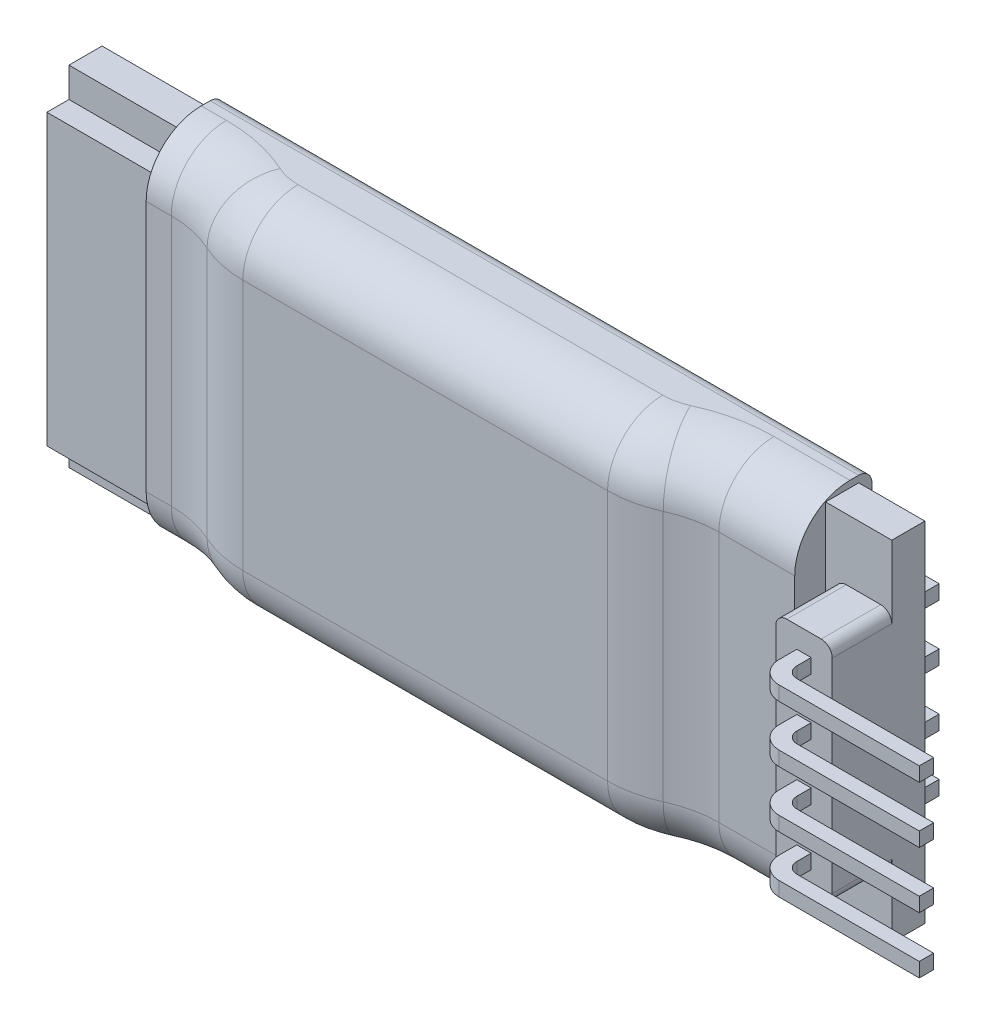
SolidWorks part; units mm, degrees
ref_plane "Přední rovina" through (0, 0, 0) normal (0, 0, 1) x (1, 0, 0)
ref_plane "Horní rovina" through (0, 0, 0) normal (0, 1, 0) x (1, 0, 0)
ref_plane "Pravá rovina" through (0, 0, 0) normal (1, 0, 0) x (0, 0, -1)
sketch "Skica1" plane through (0, 0, 0) normal (0, 0, 1) x (1, 0, 0)
  line L0 (0, 0) -> (-5.05, 0) construction
  line L1 (18.65, -7.9) -> (-18.65, -7.9)
  line L2 (18.65, -7.9) -> (18.65, 7.9)
  line L3 (18.65, 7.9) -> (-18.65, 7.9)
  line L4 (-18.65, -7.9) -> (-18.65, 7.9)
  line L5 (18.65, -7.9) -> (-18.65, 7.9) construction
  line L6 (18.65, 7.9) -> (-18.65, -7.9) construction
  line L7 (8.55, -6.55) -> (-18.65, -6.55)
  line L8 (8.55, -6.55) -> (8.55, 6.55)
  line L9 (8.55, 6.55) -> (-18.65, 6.55)
  line L10 (-18.65, -6.55) -> (-18.65, 6.55)
  line L11 (8.55, -6.55) -> (-18.65, 6.55) construction
  line L12 (8.55, 6.55) -> (-18.65, -6.55) construction
  point P0 (0, 0)
  point P6 (-5.05, 0)
  dimension "D1" = 15.8
  dimension "D2" = 37.3
  dimension "D3" = 13.1
  dimension "D4" = 27.2
extrude "Přidat vysunutím1" add sketch "Skica1" against normal blind 1.5 contours L3 L4 L1 L2
extrude "Přidat vysunutím2" add sketch "Skica1<3>" along normal blind 1 contours L8 L9 L4 L7 region at (-5.05, 0, 0)
sketch "Skica1<3>" plane through (0, 0, 0) normal (0, 0, 1) x (1, 0, 0) same geometry as "Skica1"
sketch "Skica2" plane through (0, 0, 0) normal (0, 0, 1) x (1, 0, 0)
  line L0 (18.65, -7.9) -> (18.65, 7.9) construction
  line L1 (16.09, -5.12) -> (18.65, -5.12)
  line L2 (16.09, -5.12) -> (16.09, 5.12)
  line L3 (16.09, 5.12) -> (18.65, 5.12)
  line L4 (18.65, -5.12) -> (18.65, 5.12)
  line L5 (16.09, -5.12) -> (18.65, 5.12) construction
  line L6 (16.09, 5.12) -> (18.65, -5.12) construction
  line L7 (0, 0) -> (17.37, 0) construction
  point P0 (17.37, 0)
  dimension "D1" = 2.56
  dimension "D2" = 10.24
extrude "Přidat vysunutím3" add sketch "Skica2" along normal blind 2.7
sketch "Skica3" plane through (0, 0, 2.7) normal (0, 0, 1) x (1, 0, 0)
  line L0 (18.65, 0) -> (16.09, 0) construction
  line L1 (18.65, -5.12) -> (18.65, 5.12) construction
  line L2 (16.09, 5.12) -> (16.09, -5.12) construction
  line L3 (17.37, -5.12) -> (17.37, 5.12) construction
  line L4 (16.09, -5.12) -> (18.65, -5.12) construction
  line L5 (18.65, 5.12) -> (16.09, 5.12) construction
  line L6 (17.695, 1.605) -> (17.045, 0.955) construction
  line L7 (17.695, -3.515) -> (17.045, -3.515)
  line L8 (17.695, -3.515) -> (17.695, -4.165)
  line L9 (17.695, -4.165) -> (17.045, -4.165)
  line L10 (17.045, -3.515) -> (17.045, -4.165)
  line L11 (17.695, -3.515) -> (17.045, -4.165) construction
  line L12 (17.695, -4.165) -> (17.045, -3.515) construction
  line L13 (17.695, -0.955) -> (17.045, -0.955)
  line L14 (17.695, -0.955) -> (17.695, -1.605)
  line L15 (17.695, -1.605) -> (17.045, -1.605)
  line L16 (17.045, -0.955) -> (17.045, -1.605)
  line L17 (17.695, -0.955) -> (17.045, -1.605) construction
  line L18 (17.695, -1.605) -> (17.045, -0.955) construction
  line L19 (17.695, 0.955) -> (17.045, 1.605) construction
  line L20 (17.695, 4.165) -> (17.045, 3.515) construction
  line L21 (17.695, 3.515) -> (17.045, 4.165) construction
  line L22 (17.045, 0.955) -> (17.045, 1.605)
  line L23 (17.695, 1.605) -> (17.045, 1.605)
  line L24 (17.695, 0.955) -> (17.695, 1.605)
  line L25 (17.695, 0.955) -> (17.045, 0.955)
  line L26 (17.045, 3.515) -> (17.045, 4.165)
  line L27 (17.695, 4.165) -> (17.045, 4.165)
  line L28 (17.695, 3.515) -> (17.695, 4.165)
  line L29 (17.695, 3.515) -> (17.045, 3.515)
  point P12 (17.37, -3.84)
  point P17 (17.37, -1.28)
  point P30 (17.37, 1.28)
  point P31 (17.37, 3.84)
  dimension "D1" = 0.65
  dimension "D2" = 2.56
  dimension "D3" = 2.56
extrude "Přidat vysunutím4" add sketch "Skica3" along normal blind 1.8 and the other way blind 5.8
sketch "Skica4" plane through (17.695, 0, 0) normal (1, 0, 0) x (0, 0, -1)
  line L0 (-2.7, -3.515) -> (-4.5, -3.515) construction
  line L1 (-4.5, -4.165) -> (-3.85, -4.165)
  line L2 (-4.5, -4.165) -> (-4.5, -3.515)
  line L3 (-4.5, -3.515) -> (-3.85, -3.515)
  line L4 (-3.85, -4.165) -> (-3.85, -3.515)
  line L5 (-2.7, -0.955) -> (-4.5, -0.955) construction
  line L6 (-4.5, -1.605) -> (-3.85, -1.605)
  line L7 (-4.5, -1.605) -> (-4.5, -0.955)
  line L8 (-4.5, -0.955) -> (-3.85, -0.955)
  line L9 (-3.85, -1.605) -> (-3.85, -0.955)
  line L10 (0, 0) -> (-5.4142, 0) construction
  line L11 (-3.85, 1.605) -> (-3.85, 0.955)
  line L12 (-4.5, 0.955) -> (-3.85, 0.955)
  line L13 (-4.5, 1.605) -> (-4.5, 0.955)
  line L14 (-4.5, 1.605) -> (-3.85, 1.605)
  line L15 (-3.85, 4.165) -> (-3.85, 3.515)
  line L16 (-4.5, 3.515) -> (-3.85, 3.515)
  line L17 (-4.5, 4.165) -> (-4.5, 3.515)
  line L18 (-4.5, 4.165) -> (-3.85, 4.165)
extrude "Přidat vysunutím5" add sketch "Skica4" along normal blind 6.7
fillet "Zaoblit1" radius 1 4 edges at (17.045, -3.84, 4.5) (17.045, -1.28, 4.5) (17.045, 1.28, 4.5) (17.045, 3.84, 4.5)
fillet "Zaoblit2" radius 0.5 4 edges at (17.695, 3.84, 3.85) (17.695, 1.28, 3.85) (17.695, -1.28, 3.85) (17.695, -3.84, 3.85)
sketch "Skica5" plane through (0, 0, -1.5) normal (0, 0, -1) x (-1, 0, 0)
  line L0 (18.65, -7.9) -> (18.65, 7.9) construction
  line L1 (-15.65, 8.2) -> (13.75, 8.2)
  line L2 (-15.65, 8.2) -> (-15.65, -8.2)
  line L3 (-15.65, -8.2) -> (13.75, -8.2)
  line L4 (13.75, 8.2) -> (13.75, -8.2)
  line L5 (-15.65, 8.2) -> (13.75, -8.2) construction
  line L6 (-15.65, -8.2) -> (13.75, 8.2) construction
  line L7 (-18.65, -7.9) -> (-18.65, 7.9) construction
  line L8 (-0.95, 0) -> (0, 0) construction
  point P0 (-0.95, 0)
  dimension "D1" = 4.9
  dimension "D2" = 3
  dimension "D3" = 16.4
extrude "Přidat vysunutím6" add sketch "Skica5" along normal blind 0.6 and the other way blind 3.8
sketch "Skica6" plane through (0, 0, 2.3) normal (0, 0, 1) x (1, 0, 0)
  line L0 (-13.75, 8.2) -> (15.65, 8.2) construction
  line L1 (15.65, -8.2) -> (9.35, -8.2)
  line L2 (15.65, -8.2) -> (15.65, 8.2)
  line L3 (15.65, 8.2) -> (9.35, 8.2)
  line L4 (9.35, -8.2) -> (9.35, 8.2)
  dimension "D1" = 6.3
extrude "Odebrat vysunutím1" cut sketch "Skica6" against normal blind 0.9
fillet "Zaoblit3" radius 5 1 edges at (9.35, 0, 1.4)
fillet "Zaoblit4" radius 5 1 edges at (9.35, 0, 2.3)
sketch "Skica7" plane through (0, 0, 2.3) normal (0, 0, 1) x (1, 0, 0)
  line L0 (8.0657, -8.2) -> (-13.75, -8.2) construction
  line L1 (-13.75, 8.2) -> (-9.75, 8.2)
  line L2 (-13.75, 8.2) -> (-13.75, -8.2)
  line L3 (-13.75, -8.2) -> (-9.75, -8.2)
  line L4 (-9.75, 8.2) -> (-9.75, -8.2)
  dimension "D1" = 4
extrude "Odebrat vysunutím2" cut sketch "Skica7" against normal blind 0.9
fillet "Zaoblit7" radius 5 1 edges at (-9.75, 0, 1.4)
fillet "Zaoblit8" radius 5 1 edges at (-9.75, 0, 2.3)
fillet "Zaoblit5" radius 2.5 14 edges at (13.9309, 8.2, 1.4) (11.1512, 8.2, 1.5138) (9.1264, 8.2, 2.1862) (13.9309, -8.2, 1.4) (11.1512, -8.2, 1.5138) (9.1264, -8.2, 2.1862) (-0.2, 8.2, 2.3) (-0.2, -8.2, 2.3) (-13.1809, 8.2, 1.4) (-11.5512, 8.2, 1.5138) (-9.5264, 8.2, 2.1862) (-13.1809, -8.2, 1.4) (-11.5512, -8.2, 1.5138) (-9.5264, -8.2, 2.1862)
fillet "Zaoblit6" radius 0.6 2 edges at (0.95, -8.2, -2.1) (0.95, 8.2, -2.1)
fillet "Zaoblit9" radius 0.5 4 edges at (18.65, -5.12, 1.35) (16.09, -5.12, 1.35) (18.65, 5.12, 1.35) (16.09, 5.12, 1.35)
fillet "Zaoblit10" radius 0.5 16 edges at (17.37, 1.605, -1.5) (17.37, -0.955, -1.5) (17.37, -3.515, -1.5) (17.045, 3.84, -1.5) (17.045, 1.28, -1.5) (17.045, -1.28, -1.5) (17.045, -3.84, -1.5) (17.37, 3.515, -1.5) (17.37, 0.955, -1.5) (17.37, -1.605, -1.5) (17.37, -4.165, -1.5) (17.695, -3.84, -1.5) (17.695, -1.28, -1.5) (17.695, 1.28, -1.5) (17.37, 4.165, -1.5) (17.695, 3.84, -1.5)
